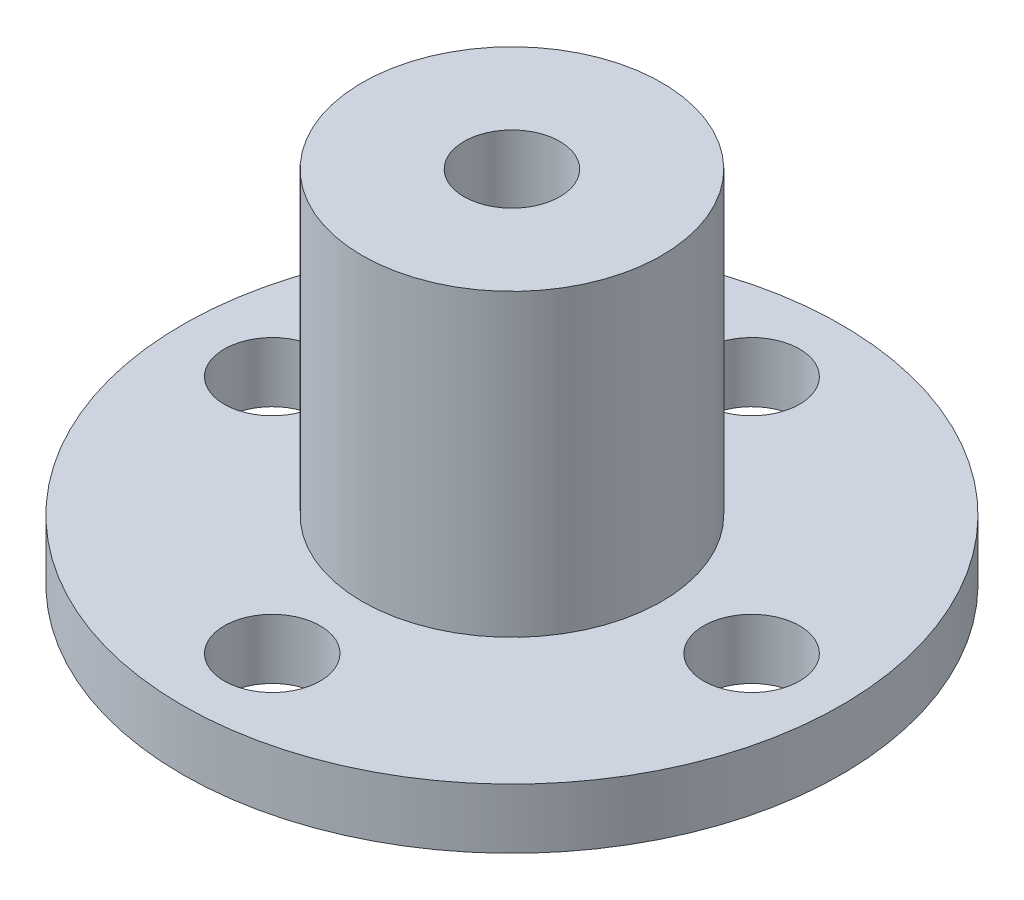
SolidWorks part; units mm, degrees
ref_plane "前视基准面" through (0, 0, 0) normal (0, 0, 1) x (1, 0, 0)
ref_plane "上视基准面" through (0, 0, 0) normal (0, 1, 0) x (1, 0, 0)
ref_plane "右视基准面" through (0, 0, 0) normal (1, 0, 0) x (0, 0, -1)
sketch "草图1" plane through (0, 0, 0) normal (0, 1, 0) x (1, 0, 0)
  circle A0 centre (0, 0) radius 11
  circle A1 centre (0, 0) radius 8
  circle A2 centre (0, 8) radius 1.6
  circle A3 centre (8, 0) radius 1.6
  circle A4 centre (0, -8) radius 1.6
  circle A5 centre (-8, 0) radius 1.6
  circle A6 centre (0, 0) radius 1.6
  circle A7 centre (0, 0) radius 5
extrude "凸台-拉伸1" add sketch "草图1" along normal blind 10 contours A7 A6 region at (-4.8586, 0, 0)
extrude "凸台-拉伸2" add sketch "草图1<3>" against normal blind 2 separate body contours A5 A1 A4 A3 A2 A7 region at (6.1783, 0, 0)
sketch "草图1<3>" plane through (0, 0, 0) normal (0, 1, 0) x (1, 0, 0) same geometry as "草图1"
extrude "凸台-拉伸3" add sketch "草图1<4>" against normal blind 2 contours A0 A5 A1 A2 A3 A4 region at (-10.6889, 0, 0)
sketch "草图1<4>" plane through (0, 0, 0) normal (0, 1, 0) x (1, 0, 0) same geometry as "草图1"
